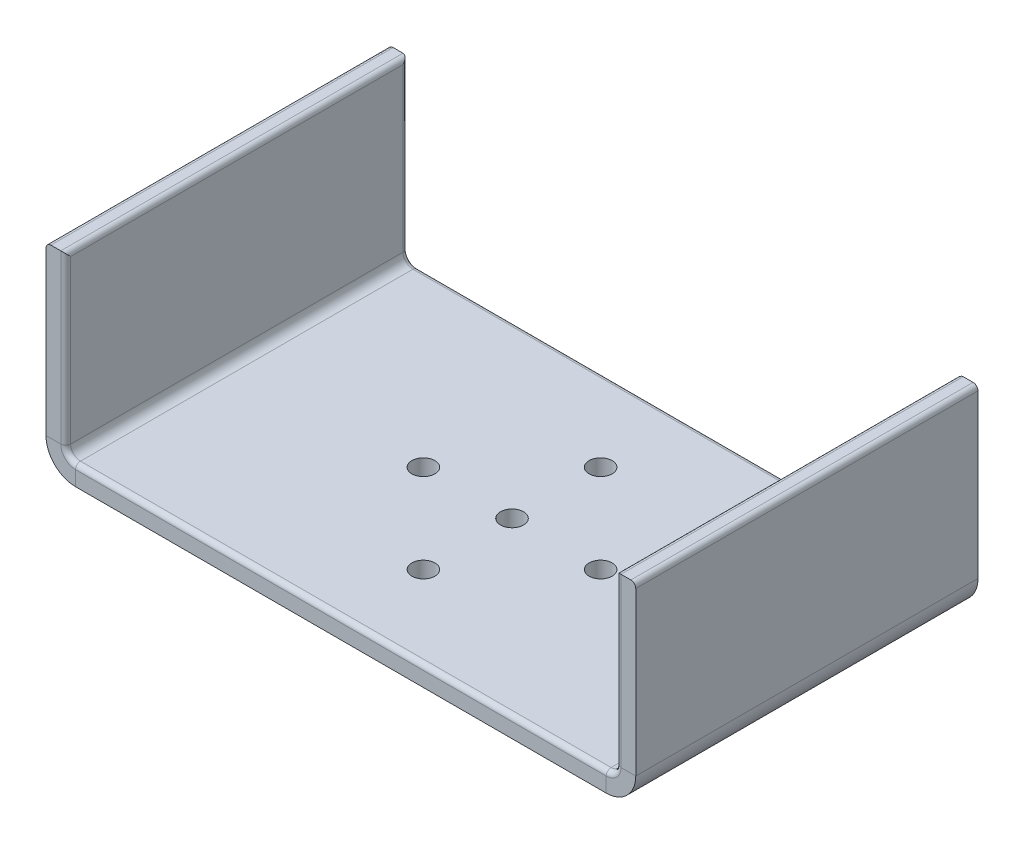
SolidWorks part; units mm, degrees
note: The reader was unsure of these and kept them because the rebuilt part matched: flange length of "Edge-Flange1".
ref_plane "前视基准面" through (0, 0, 0) normal (0, 0, 1) x (1, 0, 0)
ref_plane "上视基准面" through (0, 0, 0) normal (0, 1, 0) x (1, 0, 0)
ref_plane "右视基准面" through (0, 0, 0) normal (1, 0, 0) x (0, 0, -1)
sketch "Sketch1" plane through (0, 0, 0) normal (0, 1, 0) x (1, 0, 0)
  line L0 (0, 17.38) -> (0, -17.38) construction
  line L1 (-29.95, 17.38) -> (29.95, 17.38)
  line L2 (-29.95, 17.38) -> (-29.95, -17.38)
  line L3 (-29.95, -17.38) -> (29.95, -17.38)
  line L4 (29.95, 17.38) -> (29.95, -17.38)
  line L5 (-29.95, 0) -> (29.95, 0) construction
  point P9 (0, 0)
  dimension "D1" = 59.9
  dimension "D2" = 34.76
base flange "Base-Flange1" sketch "Sketch1" thickness 2 reverse thickness direction no parameters "D1"=0.7366
edge flange "Edge-Flange1" sketch "Sketch6" flange profiles "Sketch6", "Sketch7" flange angle 90 flange length 20 flange position material inside bend radius 1 thickness 2 relief rectangular parameters "D6"=10, "D8"=1
sketch "Sketch6" plane through (-29.95, 0, 0) normal (-1, 0, 0) x (0, 0, 1)
  line L2 (-17.38, 0) -> (-17.38, 18)
  line L3 (-17.38, 18) -> (17.38, 18)
  line L4 (17.38, 18) -> (17.38, 0)
  line L5 (-17.38, 0) -> (17.38, 0) construction
  line L6 (-17.38, 0) -> (17.38, 0)
sketch "Sketch7" plane through (29.95, 0, 0) normal (1, 0, 0) x (0, 0, -1)
  line L0 (-17.38, 0) -> (17.38, 0) construction
  line L1 (-17.38, 0) -> (17.38, 0)
  line L2 (-17.38, 0) -> (-17.38, 18)
  line L3 (-17.38, 18) -> (17.38, 18)
  line L4 (17.38, 18) -> (17.38, 0)
bend "EdgeBend1" bend radius 1 bend angle 90 parameters "D5"=1
bend "EdgeBend2" bend radius 1 bend angle 90 parameters "D5"=2
fillet "Fillet1" radius 0.5 14 edges at (0, 0, 17.38) (0, 0, -17.38) (-27.6571, 0.2929, -17.38) (-27.6571, 0.2929, 17.38) (-27.95, 9.5, 17.38) (-27.95, 9.5, -17.38) (-29.95, 18, 0) (-27.95, 18, 0) (27.6571, 0.2929, 17.38) (27.6571, 0.2929, -17.38) (27.95, 9.5, 17.38) (27.95, 9.5, -17.38) (29.95, 18, 0) (27.95, 18, 0)
sketch "Sketch8" plane through (0, 0, 0) normal (0, 1, 0) x (1, 0, 0)
  circle A0 centre (0, 0) radius 1.17
  circle A1 centre (0, 9) radius 1.17
  circle A2 centre (9, 0) radius 1.17
  circle A3 centre (0, -9) radius 1.17
  circle A4 centre (-9, 0) radius 1.17
  point P5 (0, 0)
  point P6 (0, 0)
  point P14 (0, 0)
  dimension "D1" = 2.34
  dimension "D2" = 2.34
  dimension "D3" = 9
  dimension "D4" = 4
extrude "Cut-Extrude1" cut sketch "Sketch8" against normal blind 10 normal cut yes
sketch "Bend-Lines1" [suppressed] plane through (0, 0, 0) normal (0, 1, 0) x (1, 0, 0)
sketch "Bounding-Box1" [suppressed] plane through (0, 0, 0) normal (0, 1, 0) x (1, 0, 0)
sheet metal parameters "Sheet-Metal7" thickness 2 parameters "D1"=0.7366
flat pattern "Flat-Pattern7" [suppressed]
sketch "Bend-Lines2" plane through (0, 0, 0) normal (0, 1, 0) x (1, 0, 0)
sketch3d "Bounding-Box2" [suppressed]
  line L0 (29.95, -17.38, 0) -> (-29.95, -17.38, 0) construction
  line L1 (29.95, 17.38, 0) -> (-29.95, 17.38, 0) construction
  line L2 (29.95, -17.38, 0) -> (29.95, 17.38, 0) construction
  line L3 (-29.95, -17.38, 0) -> (-29.95, 17.38, 0) construction
sheet metal parameters "Sheet-Metal8" thickness 2 parameters "D1"=0.7366
flat pattern "Flat-Pattern7" [suppressed]
sketch "Bend-Lines2"
sketch3d "Bounding-Box2" [suppressed]
  line L0 (29.95, -17.38, 0) -> (-29.95, -17.38, 0) construction
  line L1 (29.95, 17.38, 0) -> (-29.95, 17.38, 0) construction
  line L2 (29.95, -17.38, 0) -> (29.95, 17.38, 0) construction
  line L3 (-29.95, -17.38, 0) -> (-29.95, 17.38, 0) construction
bend of the flat pattern "Flatten-<EdgeBend1>1"
bend of the flat pattern "Flatten-<EdgeBend2>1"
sheet metal parameters "Sheet-Metal9" thickness 2 parameters "D1"=0.7366
flat pattern "Flat-Pattern7" [suppressed]
sketch "Bend-Lines2" plane through (0, 0, 0) normal (0, 1, 0) x (1, 0, 0)
sketch3d "Bounding-Box2" [suppressed]
  line L0 (29.95, -17.38, 0) -> (-29.95, -17.38, 0) construction
  line L1 (29.95, 17.38, 0) -> (-29.95, 17.38, 0) construction
  line L2 (29.95, -17.38, 0) -> (29.95, 17.38, 0) construction
  line L3 (-29.95, -17.38, 0) -> (-29.95, 17.38, 0) construction
bend of the flat pattern "Flatten-<EdgeBend1>1"
bend of the flat pattern "Flatten-<EdgeBend2>1"
